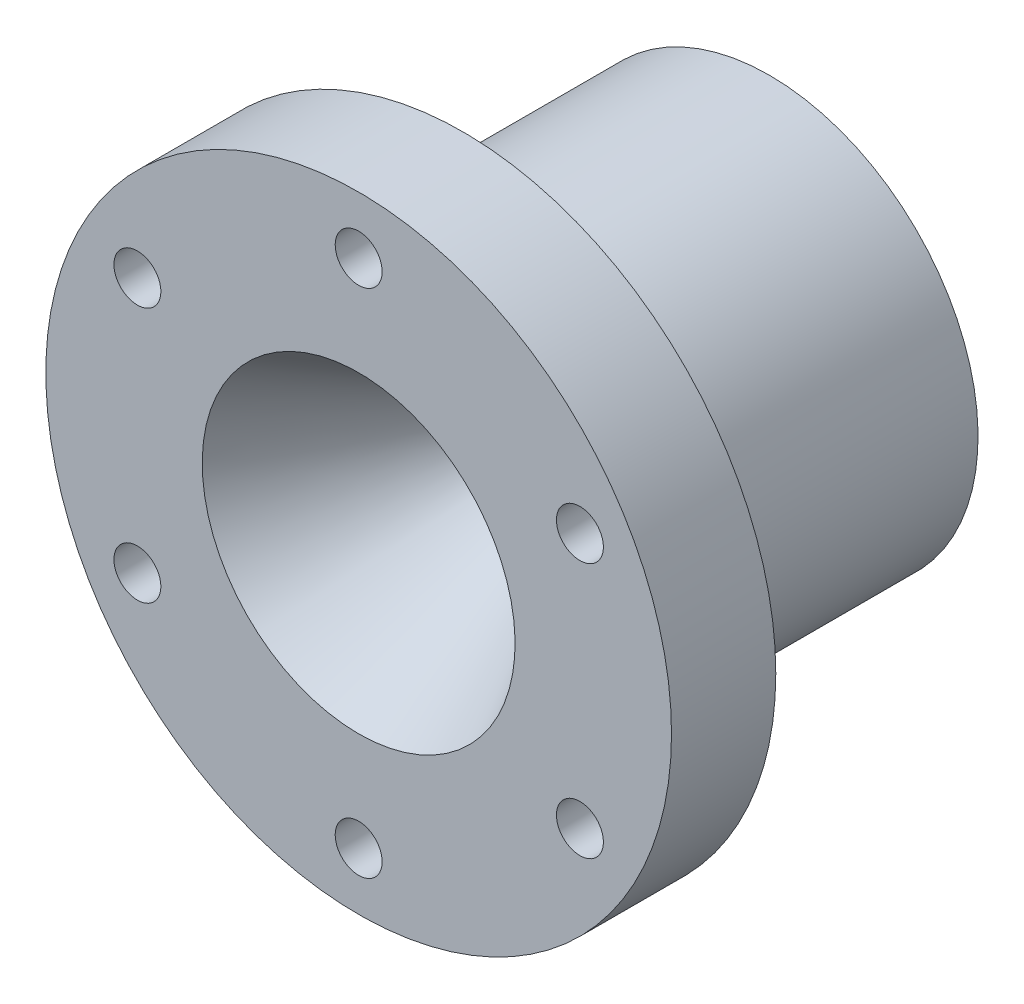
SolidWorks part; units mm, degrees
ref_plane "Front Plane" through (0, 0, 0) normal (0, 0, 1) x (1, 0, 0)
ref_plane "Top Plane" through (0, 0, 0) normal (0, 1, 0) x (1, 0, 0)
ref_plane "Right Plane" through (0, 0, 0) normal (1, 0, 0) x (0, 0, -1)
sketch "Sketch2" plane through (0, 0, 0) normal (1, 0, 0) x (0, 0, -1)
  line L1 (21.3287, 20) -> (21.3287, 10.285)
  line L2 (21.3287, 10.285) -> (0, 4.57)
  line L3 (0, 4.57) -> (-18.0653, 15)
  line L4 (-18.0653, 15) -> (-18.0653, 20)
  line L6 (-18.0653, 20) -> (21.3287, 20)
  line L7 (0, 0) -> (60, 0) construction
  line L8 (0, 0) -> (-60, 0) construction
  point P7 (-17.2114, 14.6136)
  point P9 (28.2034, 10.285)
  point P11 (0, 0)
  dimension "D1" = 4.57
  dimension "D2" = 120
  dimension "D3" = 60
  dimension "D4" = 10.285
  dimension "D5" = 20
  dimension "D6" = 105
  dimension "D7" = 120
  dimension "D8" = 15
revolve "Revolve1" add sketch "Sketch2" angle 360 about L8
sketch "Sketch3" plane through (0, 0, 18.0653) normal (0, 0, 1) x (1, 0, 0)
  circle A0 centre (0, 0) radius 30
  circle A1 centre (0, 0) radius 20 construction
  circle A2 centre (0, 0) radius 20
  dimension "D1" = 60
extrude "Boss-Extrude1" add sketch "Sketch3" against normal blind 10
hole_wizard "CBORE for M4 Hex Socket Head Cap Screw1" positions "Sketch4" profile "Sketch5" counterbore size "M4" standard "ISO" end condition through all
sketch "Sketch4" plane through (0, 0, 8.0653) normal (0, 0, -1) x (-1, 0, 0)
  point P0 (0, 24.5)
  dimension "D1" = 24.5
sketch "Sketch5" plane through (0, 24.5, 8.0653) normal (1, 0, 0) x (0, 1, 0)
  line L0 (0, 0) -> (0, 10)
  line L1 (0, 10) -> (2.25, 10)
  line L3 (2.25, 10) -> (2.25, 4.4)
  line L4 (4, 4.4) -> (2.25, 4.4)
  line L5 (4, 4.4) -> (4, 0.025)
  line L6 (4, 0.025) -> (4.025, 0)
  line L7 (4.025, 0) -> (0, 0)
  line L8 (-4, 0.025) -> (-4.025, 0) construction
  line L11 (0, -6.35) -> (0, 107.95) construction
  dimension "Thru Hole Dia." = 4.5
  dimension "Thru Hole Depth" = 10
  dimension "C'Bore Dia." = 8
  dimension "C'Bore Depth" = 4.4
  dimension "Near C'Sink Dia." = 8.05
  dimension "Near C'Sink Angle" = 90
pattern_circular "CirPattern1" count 6 over 360 about axis through (0, 0, 8.0653) along (0, 0, 1) of "CBORE for M4 Hex Socket Head Cap Screw1"
